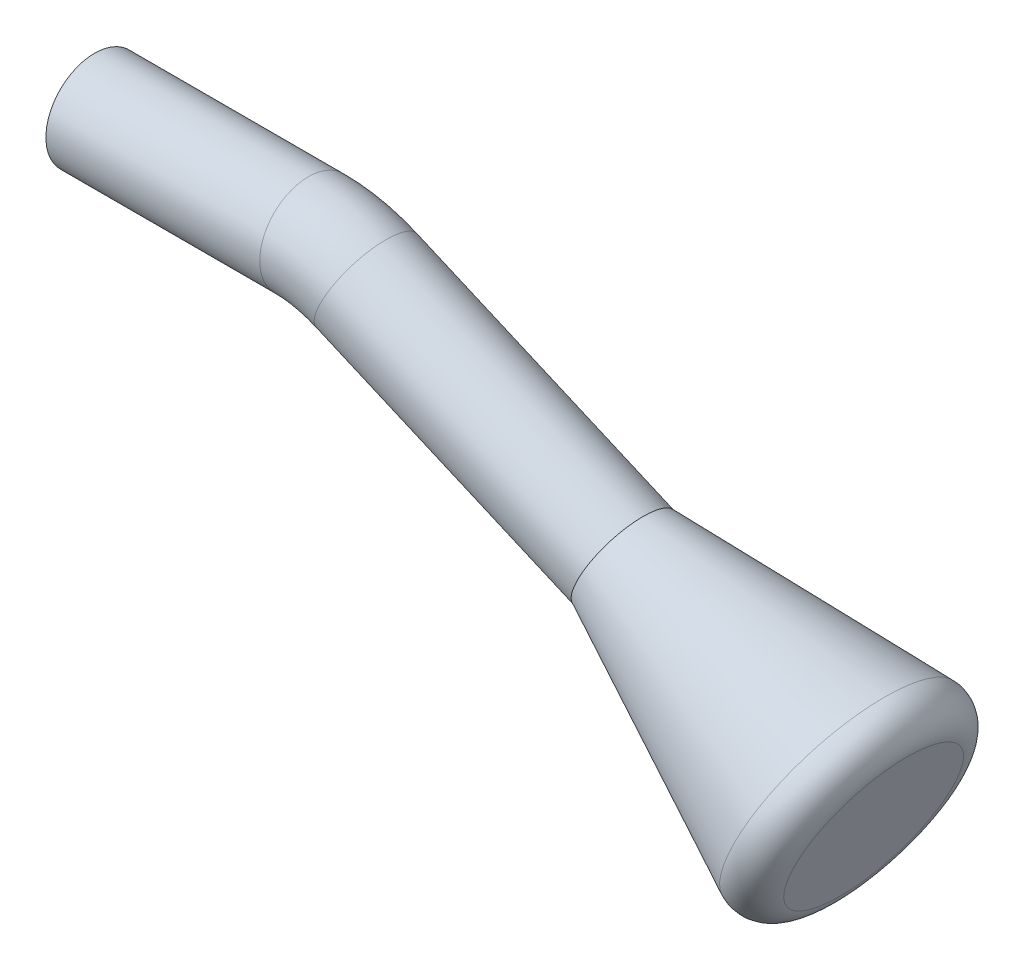
SolidWorks part; units mm, degrees
ref_plane "Спереди" through (0, 0, 0) normal (0, 0, 1) x (1, 0, 0)
ref_plane "Сверху" through (0, 0, 0) normal (0, 1, 0) x (1, 0, 0)
ref_plane "Справа" through (0, 0, 0) normal (1, 0, 0) x (0, 0, -1)
sketch "Эскиз1" plane through (0, 0, 0) normal (0, 0, 1) x (1, 0, 0)
  line L0 (0, 0) -> (21.9586, 0)
  line L1 (27.9151, -1.2334) -> (80, -23.7694)
  line L2 (27.9151, -1.2334) -> (21.9586, -15) construction
  line L3 (21.9586, -15) -> (21.9586, 0) construction
  line L4 (21.9586, 0) -> (27.9151, -1.2334) construction
  line L5 (21.9586, -15) -> (25, -0.3116) construction
  arc A0 (21.9586, 0) -> (27.9151, -1.2334) centre (21.9586, -15) cw
  point P9 (21.9586, 0)
  dimension "D1" = 15
  dimension "D2" = 25
  dimension "D3" = 80
sketch "Эскиз2" plane through (0, 0, 0) normal (1, 0, 0) x (0, 0, -1)
  circle A0 centre (0, 0) radius 5
  dimension "D1" = 10
sweep "По траектории1" add profiles "Эскиз2" path "Эскиз1"
sketch "Эскиз3" plane through (76.0476, -32.9042, 0) normal (0.9178, -0.3971, 0) x (0, 0, -1)
  circle A0 centre (0, 9.9532) radius 12.5
  circle A1 centre (0, 9.9532) radius 5 construction
  dimension "D1" = 25
extrude "Бобышка-Вытянуть1" add sketch "Эскиз3" against normal blind 30 draft 15
fillet "Скругление2" radius 3 1 edges at (84.9638, -12.2972, 0)
